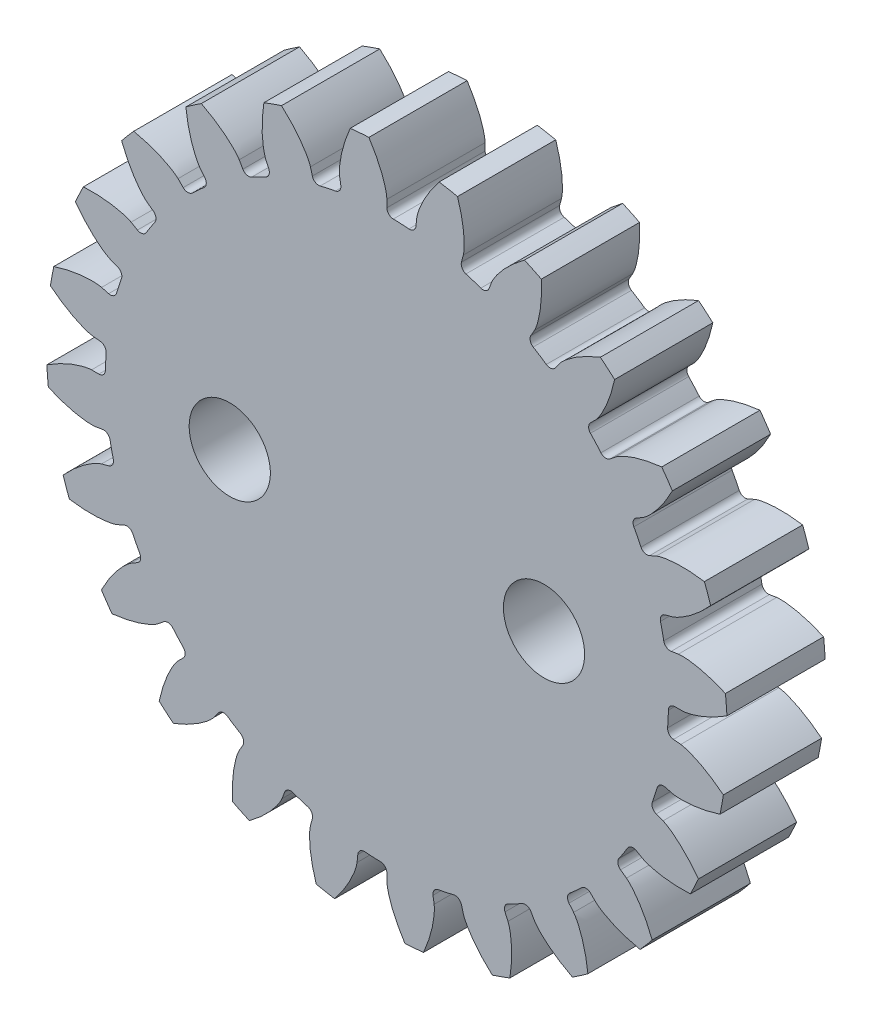
SolidWorks part; units mm, degrees
material "7075-O (SS)"
ref_plane "Front" through (0, 0, 0) normal (0, 0, 1) x (1, 0, 0)
ref_plane "Top" through (0, 0, 0) normal (0, 1, 0) x (1, 0, 0)
ref_plane "Right" through (0, 0, 0) normal (1, 0, 0) x (0, 0, -1)
sketch "ｽｹｯﾁ1" plane through (0, 0, 0) normal (0, 0, 1) x (1, 0, 0)
  line L0 (22.5526, 0) -> (0, 0) construction
  line L1 (22.5526, 0) -> (21.5, 0)
  line L2 (0, 0) -> (25.9668, -1.3136)
  circle A0 centre (0, 0) radius 22.5526 construction
  circle A1 centre (0, 0) radius 21.5 construction
  circle A2 centre (0, 0) radius 24 construction
  circle A3 centre (0, 0) radius 26
  arc A4 (21.5, 0) -> (21.4725, -1.0863) centre (0, 0) cw
  arc A5 (23.9973, 0.3577) -> (23.9693, -1.2126) centre (0, 0) cw
  spline S0 degree 4 poles (22.5526, 0) (22.5874, 0.0011) (22.6567, 0.0054) (22.8505, 0.0283) (23.2156, 0.0999) (23.764, 0.2576) (24.4933, 0.5458) (25.3932, 1.0005) (26.3919, 1.6314) (27.421, 2.4222) (28.4509, 3.3688) (29.4028, 4.3935) (30.2783, 5.4838) (31.1188, 6.6866) (32.0583, 8.2419) (33.024, 10.183) (33.9312, 12.5326) (34.6768, 15.2302) (35.1717, 17.9843) (35.4277, 20.7703) (35.4563, 23.5676) (35.2683, 26.3585) (34.9241, 28.7814) (34.5417, 30.6653) (34.2091, 32.0222) (33.9364, 33.0347) (33.6419, 34.0391) (33.318, 35.0387) (32.9699, 36.023) (32.6584, 36.8453) (32.4056, 37.4843) (32.1525, 38.0917) (31.9408, 38.5845) (31.6913, 39.1427) (31.5261, 39.5026) (31.2539, 40.0814) (31.0342, 40.5277) (30.7638, 41.0681) (30.5147, 41.5456) (30.242, 42.0581) (29.9755, 42.5406) (29.7632, 42.9175) (29.6249, 43.1564) (29.5531, 43.2804) knots 0 0 0 0 0 0.002802 0.005604 0.015718 0.02996 0.048734 0.068727 0.096889 0.125051 0.153212 0.181374 0.209535 0.237696 0.271429 0.327752 0.384075 0.440398 0.496721 0.553044 0.609367 0.66569 0.722013 0.750174 0.764255 0.778336 0.806497 0.834659 0.84874 0.86282 0.876901 0.890982 0.900036 0.909091 0.920455 0.931818 0.943182 0.954545 0.965909 0.977273 0.988636 1 1 1 1 1 construction
  spline S1 degree 4 poles (22.5526, 0) (22.5874, 0.0011) (22.6567, 0.0054) (22.8505, 0.0283) (23.2156, 0.0999) (23.764, 0.2576) (24.4933, 0.5458) (25.3932, 1.0005) (26.3919, 1.6314) (27.421, 2.4222) (28.4509, 3.3688) (29.4028, 4.3935) (30.2783, 5.4838) (31.1188, 6.6866) (32.0583, 8.2419) (33.024, 10.183) (33.9312, 12.5326) (34.6768, 15.2302) (35.1717, 17.9843) (35.4277, 20.7703) (35.4563, 23.5676) (35.2683, 26.3585) (34.9241, 28.7814) (34.5417, 30.6653) (34.2091, 32.0222) (33.9364, 33.0347) (33.6419, 34.0391) (33.318, 35.0387) (32.9699, 36.023) (32.6584, 36.8453) (32.4056, 37.4843) (32.1525, 38.0917) (31.9408, 38.5845) (31.7564, 38.9971) (31.6714, 39.1846) (31.6289, 39.2774) knots 0 0 0 0 0 0.002802 0.005604 0.015718 0.02996 0.048734 0.068727 0.096889 0.125051 0.153212 0.181374 0.209535 0.237696 0.271429 0.327752 0.384075 0.440398 0.496721 0.553044 0.609367 0.66569 0.722013 0.750174 0.764255 0.778336 0.806497 0.834659 0.84874 0.86282 0.876901 0.890982 0.900036 0.909091 0.909091 0.909091 0.909091 0.909091
  dimension "歯先円直径" = 52
  dimension "基礎円直径" = 45.1052
  dimension "基礎ピッチ円直径" = 48
  dimension "全歯たけ" = 4.5
  dimension "基準ピッチ/4" = 1.5708
sketch "ｽｹｯﾁ3" plane through (0, 0, 0) normal (0, 0, 1) x (1, 0, 0)
  circle A0 centre (0, 0) radius 26 construction
  circle A1 centre (0, 0) radius 26
extrude "ﾎﾞｽ - 押し出し2" add sketch "ｽｹｯﾁ3" along normal blind 7.5
sketch "ｽｹｯﾁ4" plane through (0, 0, 0) normal (0, 0, 1) x (1, 0, 0)
  line L0 (0, 0) -> (25.9668, -1.3136) construction
  line L1 (22.5526, 0) -> (21.5, 0) construction
  line L2 (21.4725, -1.0863) -> (25.9668, -1.3136)
  line L3 (22.5526, 0) -> (21.5, 0)
  arc A1 (21.4725, -1.0863) -> (21.5, 0) centre (0, 0) ccw construction
  circle A2 centre (0, 0) radius 26 construction
  arc A3 (21.4725, -1.0863) -> (21.5, 0) centre (0, 0) ccw
  arc A4 (25.9668, -1.3136) -> (25.9637, 1.373) centre (0, 0) ccw
  spline S1 degree 4 poles (15.1862, -999.773) (16.9514, 36.3954) (19.0933, 0.7282) (21.1742, -0.3006) (23.2156, 0.0999) (23.764, 0.2576) (24.4933, 0.5458) (25.3932, 1.0005) (26.3919, 1.6314) (27.421, 2.4222) (28.4509, 3.3688) (29.4028, 4.3935) (30.2783, 5.4838) (31.1188, 6.6866) (32.0583, 8.2419) (33.024, 10.183) (33.9312, 12.5326) (34.6768, 15.2302) (35.1717, 17.9843) (35.4277, 20.7703) (35.4563, 23.5676) (35.2683, 26.3585) (34.9241, 28.7814) (34.5417, 30.6653) (34.2091, 32.0222) (33.9364, 33.0347) (33.6419, 34.0391) (33.318, 35.0387) (32.9699, 36.023) (32.6584, 36.8453) (32.4056, 37.4843) (32.1525, 38.0917) (31.3467, 39.9673) (29.663, 43.4627) (43.99, 11.7586) (-384.9057, 948.343) knots -0.13757 -0.13757 -0.13757 -0.13757 -0.13757 0.002802 0.005604 0.015718 0.02996 0.048734 0.068727 0.096889 0.125051 0.153212 0.181374 0.209535 0.237696 0.271429 0.327752 0.384075 0.440398 0.496721 0.553044 0.609367 0.66569 0.722013 0.750174 0.764255 0.778336 0.806497 0.834659 0.84874 0.86282 0.876901 0.890982 0.900036 1.038953 1.038953 1.038953 1.038953 1.038953 only from (22.5526, 0) to (31.6289, 39.2774) construction
  spline S2 degree 4 poles (22.5526, 0) (22.5874, 0.0011) (22.6567, 0.0054) (22.8505, 0.0283) (23.2156, 0.0999) (23.764, 0.2576) (24.4933, 0.5458) (25.1482, 0.8767) (25.6277, 1.1589) (25.9005, 1.3322) (25.9637, 1.373) knots 0 0 0 0 0 0.002802 0.005604 0.015718 0.02996 0.048734 0.068727 0.074792 0.074792 0.074792 0.074792 0.074792
extrude "ｶｯﾄ - 押し出し2" cut sketch "ｽｹｯﾁ4" along normal through all
pattern_circular "円形ﾊﾟﾀｰﾝ1" count 24 over 360 about axis through (0, 0, 7.5) along (0, 0, -1) of "ｶｯﾄ - 押し出し2"
mirror "ﾐﾗｰ1" about plane through (21.4725, -1.0863, 7.5) normal (0.0505, 0.9987, 0) of "円形ﾊﾟﾀｰﾝ1"
sketch "ｽｹｯﾁ5" plane through (0, 0, 7.5) normal (0, 0, 1) x (1, 0, 0)
  circle A0 centre (0, 0) radius 5.1
  dimension "D1" = 10.2
extrude "ｶｯﾄ - 押し出し3" [suppressed] cut sketch "ｽｹｯﾁ5" against normal through all
fillet "ﾌｨﾚｯﾄ5" radius 0.5 48 edges at (19.6094, 8.8161, 3.75) (18.6195, 10.75, 3.75) (16.6594, 13.5909, 3.75) (15.2028, 15.2028, 3.75) (12.5742, 17.4396, 3.75) (10.75, 18.6195, 3.75) (7.632, 20.0998, 3.75) (5.5646, 20.7674, 3.75) (2.1697, 21.3902, 3.75) (0, 21.5, 3.75) (-3.4404, 21.223, 3.75) (-5.5646, 20.7674, 3.75) (-8.8161, 19.6094, 3.75) (-10.75, 18.6195, 3.75) (-13.5909, 16.6594, 3.75) (-15.2028, 15.2028, 3.75) (-17.4396, 12.5742, 3.75) (-18.6195, 10.75, 3.75) (-20.0998, 7.632, 3.75) (-20.7674, 5.5646, 3.75) (-21.3902, 2.1697, 3.75) (-21.5, 0, 3.75) (-21.223, -3.4404, 3.75) (-20.7674, -5.5646, 3.75) (-19.6094, -8.8161, 3.75) (-18.6195, -10.75, 3.75) (-16.6594, -13.5909, 3.75) (-15.2028, -15.2028, 3.75) (-12.5742, -17.4396, 3.75) (-10.75, -18.6195, 3.75) (-7.632, -20.0998, 3.75) (-5.5646, -20.7674, 3.75) (-2.1697, -21.3902, 3.75) (0, -21.5, 3.75) (3.4404, -21.223, 3.75) (5.5646, -20.7674, 3.75) (8.8161, -19.6094, 3.75) (10.75, -18.6195, 3.75) (13.5909, -16.6594, 3.75) (15.2028, -15.2028, 3.75) (17.4396, -12.5742, 3.75) (18.6195, -10.75, 3.75) (20.0998, -7.632, 3.75) (20.7674, -5.5646, 3.75) (21.3902, -2.1697, 3.75) (21.5, 0, 3.75) (21.223, 3.4404, 3.75) (20.7674, 5.5646, 3.75)
sketch "ｽｹｯﾁ10" plane through (0, 0, 0) normal (0, 0, -1) x (-1, 0, 0)
  line L0 (12, 0) -> (-12, 0) construction
  circle A0 centre (-12, 0) radius 3.1
  circle A1 centre (12, 0) radius 3.1
  point P4 (0, 0)
  dimension "D1" = 24
  dimension "D2" = 6.2
extrude "ｶｯﾄ - 押し出し4" cut sketch "ｽｹｯﾁ10" against normal through all
equation "\"モジュール\"= 2"
equation "\"歯数\"= 24"
equation "\"圧力角\"= 20"
equation "\"歯幅\"= 7.5"
equation "\"D1@ﾎﾞｽ - 押し出し2\"=\"歯幅\""
equation "\"D1@円形ﾊﾟﾀｰﾝ1\"=\"歯数\""
equation "\"歯先円直径@ｽｹｯﾁ1\"=(\"歯数\"+2)*(\"モジュール\")"
equation "\"基礎円直径@ｽｹｯﾁ1\"=\"歯数\"*\"モジュール\"*cos(\"圧力角\")"
equation "\"全歯たけ@ｽｹｯﾁ1\"= \"モジュール\" * 2.25"
equation "\"基礎ピッチ円直径@ｽｹｯﾁ1\"=\"歯数\"*\"モジュール\""
equation "\"基準ピッチ/4@ｽｹｯﾁ1\" = PI * \"モジュール\" / 4"
